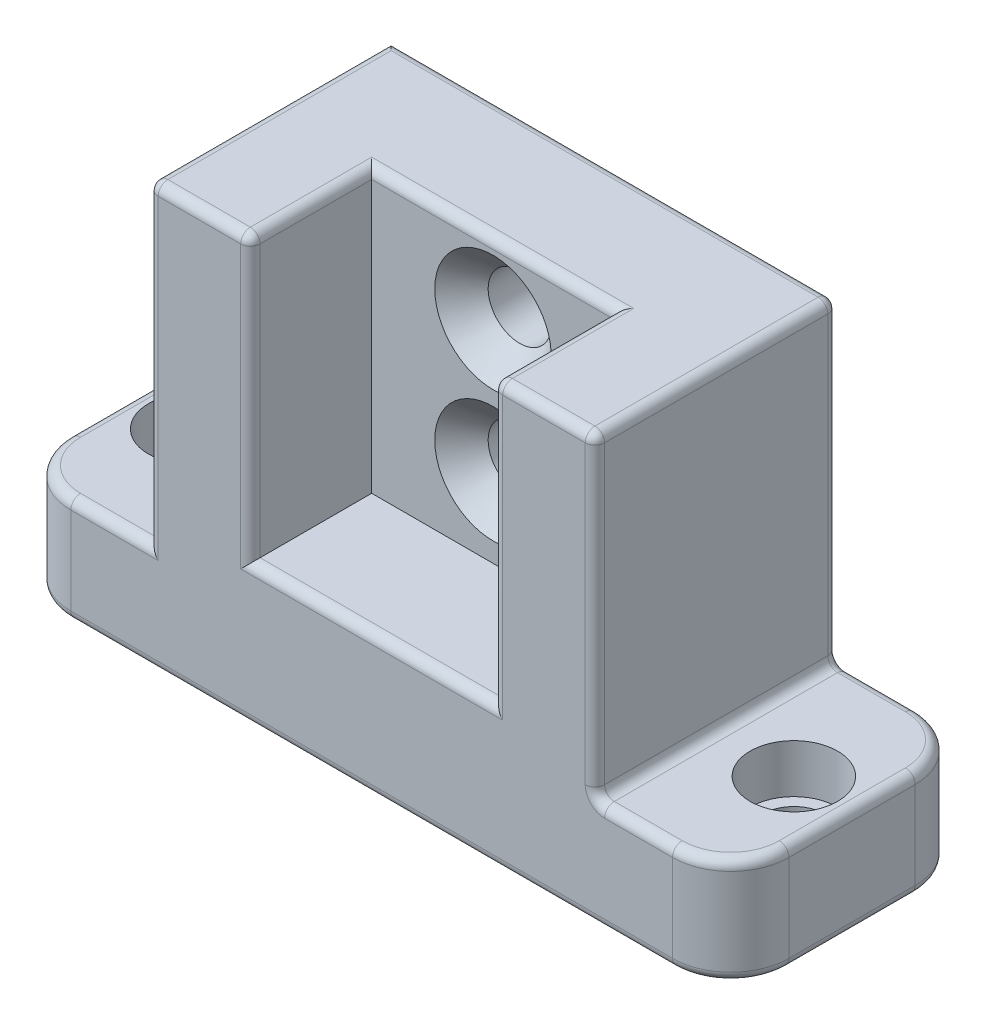
SolidWorks part; units mm, degrees
ref_plane "Front Plane" through (0, 0, 0) normal (0, 0, 1) x (1, 0, 0)
ref_plane "Top Plane" through (0, 0, 0) normal (0, 1, 0) x (1, 0, 0)
ref_plane "Right Plane" through (0, 0, 0) normal (1, 0, 0) x (0, 0, -1)
sketch "Sketch1" plane through (0, 0, 0) normal (0, 0, 1) x (1, 0, 0)
  line L0 (0, 87) -> (0, 0) construction
  line L1 (74, 0) -> (-74, 0)
  line L2 (-74, 0) -> (-74, 22)
  line L3 (-74, 22) -> (-46, 22)
  line L4 (-46, 22) -> (-46, 87)
  line L5 (-46, 87) -> (46, 87)
  line L6 (46, 22) -> (46, 87)
  line L7 (74, 22) -> (46, 22)
  line L8 (74, 0) -> (74, 22)
  point P9 (0, 87)
  dimension "D1" = 74
  dimension "D2" = 22
  dimension "D3" = 28
  dimension "D4" = 87
extrude "Boss-Extrude1" add sketch "Sketch1" along normal blind 50
sketch "Sketch2" plane through (0, 87, 0) normal (0, 1, 0) x (1, 0, 0)
  line L0 (46, -50) -> (-46, -50) construction
  line L2 (-25, -25) -> (-25, -50)
  line L3 (-25, -50) -> (25, -50)
  line L4 (25, -25) -> (25, -50)
  line L5 (-46, -50) -> (-46, 0) construction
  line L6 (46, 0) -> (-46, 0) construction
  line L7 (0, -50) -> (0, -67.2623) construction
  line L8 (25, -25) -> (-25, -25)
  point P0 (0, -25)
  point P13 (0, -25)
  dimension "D1" = 21
  dimension "D2" = 50
  dimension "D3" = 25
extrude "Cut-Extrude2" cut sketch "Sketch2" against normal blind 58 contours L2 L3 L4 L8
sketch "Sketch3" plane through (0, 22, 0) normal (0, 1, 0) x (1, 0, 0)
  circle A0 centre (62, -25) radius 9
  circle A1 centre (62, -25) radius 6.5
  dimension "D2" = 18
  dimension "D3" = 13
  dimension "D1" = 62
extrude "Cut-Extrude3" cut sketch "Sketch3" against normal blind 58 contours A1
extrude "Cut-Extrude4" cut sketch "Sketch3<3>" against normal blind 10
sketch "Sketch3<3>" plane through (0, 22, 0) normal (0, 1, 0) x (1, 0, 0) same geometry as "Sketch3"
mirror "Mirror2" about plane through (0, 0, 0) normal (1, 0, 0) of "Cut-Extrude4", "Cut-Extrude3"
sketch "Sketch6" plane through (0, 0, 0) normal (0, 0, -1) x (-1, 0, 0)
  line L0 (-46, 87) -> (46, 87) construction
  circle A0 centre (0, 72) radius 6.5
  dimension "D2" = 13
  dimension "D1" = 15
extrude "Cut-Extrude5" cut sketch "Sketch6" against normal blind 19.5
extrude "Cut-Extrude9" cut sketch "Sketch6<3>" against normal blind 8.5 draft 45 from offset 19.5 draft outward yes offset against normal yes
sketch "Sketch6<3>" plane through (0, 0, 0) normal (0, 0, -1) x (-1, 0, 0) same geometry as "Sketch6"
ref_plane "Plane1" through (0, 58.5, 0) normal (0, 1, 0) x (1, 0, 0)
mirror "Mirror3" about plane through (0, 58.5, 0) normal (0, 1, 0) of "Cut-Extrude9", "Cut-Extrude5"
fillet "Fillet1" radius 12 4 edges at (-74, 11, 0) (-74, 11, 50) (74, 11, 0) (74, 11, 50)
fillet "Fillet2" radius 2 33 edges at (54, 22, 0) (70.4853, 22, 3.5147) (74, 22, 25) (70.4853, 22, 46.4853) (-70.4853, 0, 46.4853) (-74, 0, 25) (-70.4853, 0, 3.5147) (0, 0, 0) (70.4853, 0, 3.5147) (74, 0, 25) (70.4853, 0, 46.4853) (-54, 22, 0) (-70.4853, 22, 3.5147) (-74, 22, 25) (-70.4853, 22, 46.4853) (46, 22, 25) (46, 54.5, 0) (-46, 54.5, 50) (-25, 58, 50) (0, 29, 50) (25, 58, 50) (46, 54.5, 50) (54, 22, 50) (0, 0, 50) (-54, 22, 50) (0, 87, 25) (-25, 87, 37.5) (-35.5, 87, 50) (-46, 87, 25) (0, 87, 0) (46, 87, 25) (35.5, 87, 50) (25, 87, 37.5)
